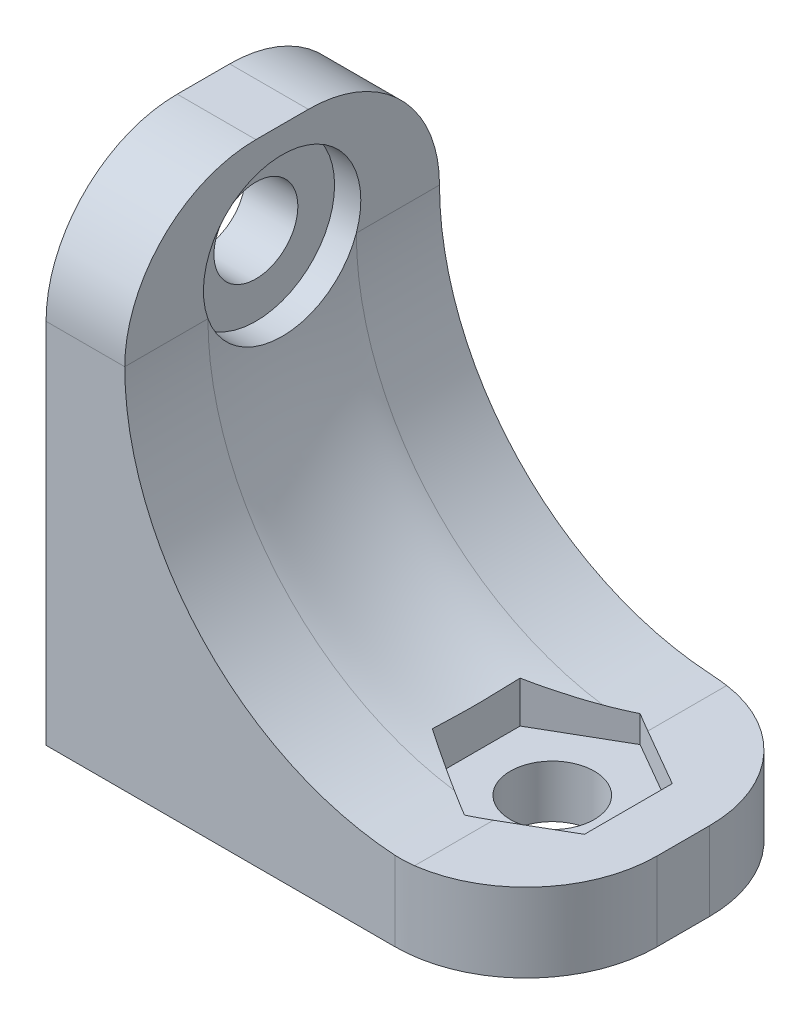
SolidWorks part; units mm, degrees
ref_plane "Alzado" through (0, 0, 0) normal (0, 0, 1) x (1, 0, 0)
ref_plane "Planta" through (0, 0, 0) normal (0, 1, 0) x (1, 0, 0)
ref_plane "Vista lateral" through (0, 0, 0) normal (1, 0, 0) x (0, 0, -1)
sketch "Croquis1" plane through (0, 0, 0) normal (0, 1, 0) x (1, 0, 0)
  line L1 (0, 0) -> (18.3, 0)
  line L2 (0, 0) -> (0, -12)
  line L3 (0, -12) -> (18.3, -12)
  line L4 (18.3, 0) -> (18.3, -12)
  circle A0 centre (13.3, -6) radius 1.6
  dimension "D2" = 3.2
  dimension "D1" = 18.3
  dimension "D3" = 12
  dimension "D4" = 5
  dimension "D5" = 6
extrude "Saliente-Extruir1" add sketch "Croquis1" along normal blind 3
sketch "Croquis2" plane through (0, 3, 0) normal (0, 1, 0) x (1, 0, 0)
  line L0 (0, -12) -> (18.3, -12) construction
  line L1 (0, 0) -> (3, 0)
  line L2 (0, 0) -> (0, -12)
  line L3 (0, -12) -> (3, -12)
  line L4 (3, 0) -> (3, -12)
  dimension "D1" = 3
extrude "Saliente-Extruir2" add sketch "Croquis2" along normal blind 16
sketch "Croquis3" plane through (3, 0, 0) normal (1, 0, 0) x (0, 0, -1)
  line L0 (-12, 19) -> (-12, 3) construction
  line L1 (-12, 3) -> (0, 3) construction
  circle A0 centre (-6, 15) radius 1.6
  dimension "D1" = 3.2
  dimension "D2" = 6
  dimension "D3" = 12
extrude "Cortar-Extruir1" cut sketch "Croquis3" against normal up to surface (3 mm away) up to face at (0, 9.5, 6)
sketch "Croquis4" plane through (3, 0, 0) normal (1, 0, 0) x (0, 0, -1)
  circle A1 centre (-6, 15) radius 3
  dimension "D1" = 6
extrude "Cortar-Extruir2" cut sketch "Croquis4" against normal blind 1
sketch "Croquis5" plane through (0, 3, 0) normal (0, 1, 0) x (1, 0, 0)
  line L0 (18.3, -12) -> (18.3, 0) construction
  line L1 (13.3, -2.6514) -> (10.4, -4.3257)
  line L2 (10.4, -4.3257) -> (10.4, -7.6743)
  line L3 (10.4, -7.6743) -> (13.3, -9.3486)
  line L4 (13.3, -9.3486) -> (16.2, -7.6743)
  line L5 (16.2, -7.6743) -> (16.2, -4.3257)
  line L6 (16.2, -4.3257) -> (13.3, -2.6514)
  circle A0 centre (13.3, -6) radius 2.9 construction
  dimension "D1" = 5.8
  dimension "D2" = 5
extrude "Cortar-Extruir3" cut sketch "Croquis5" against normal blind 1
fillet "Redondeo1" radius 11 1 edges at (3, 3, 6)
fillet "Redondeo2" radius 5 4 edges at (18.3, 1.5, 0) (18.3, 1.5, 12) (1.5, 19, 12) (1.5, 19, 0)
